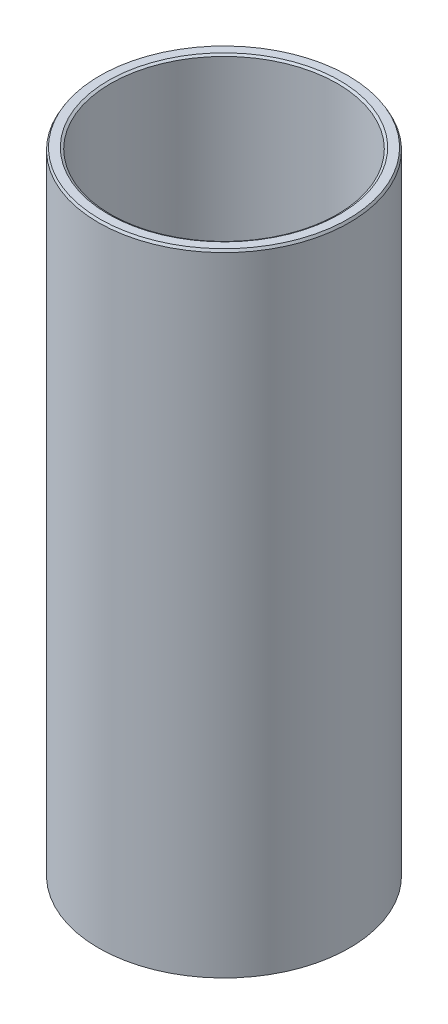
SolidWorks part; units mm, degrees
ref_plane "Front Plane" through (0, 0, 0) normal (0, 0, 1) x (1, 0, 0)
ref_plane "Top Plane" through (0, 0, 0) normal (0, 1, 0) x (1, 0, 0)
ref_plane "Right Plane" through (0, 0, 0) normal (1, 0, 0) x (0, 0, -1)
sketch "Sketch1" plane through (0, 0, 0) normal (0, 1, 0) x (1, 0, 0)
  circle A0 centre (0, 0) radius 55
  dimension "SLEEVE_OD" = 110
extrude "Boss-Extrude1" add sketch "Sketch1" along normal blind 276.86
sketch "Sketch2" plane through (0, 0, 0) normal (0, 1, 0) x (1, 0, 0)
  circle A0 centre (0, 0) radius 49.6648
  dimension "BORE_D" = 99.3295
extrude "Cut-Extrude1" cut sketch "Sketch2" along normal through all
chamfer "Chamfer1" distance 1.0511 angle 30 4 edges at (0, 276.86, 49.6648) (0, 0, 49.6648) (0, 0, 55) (0, 276.86, 55) first distance on face at (0, 276.86, 49.6648) first distance on face at (0, 0, 49.6648) first distance on face at (0, 276.86, 55)
